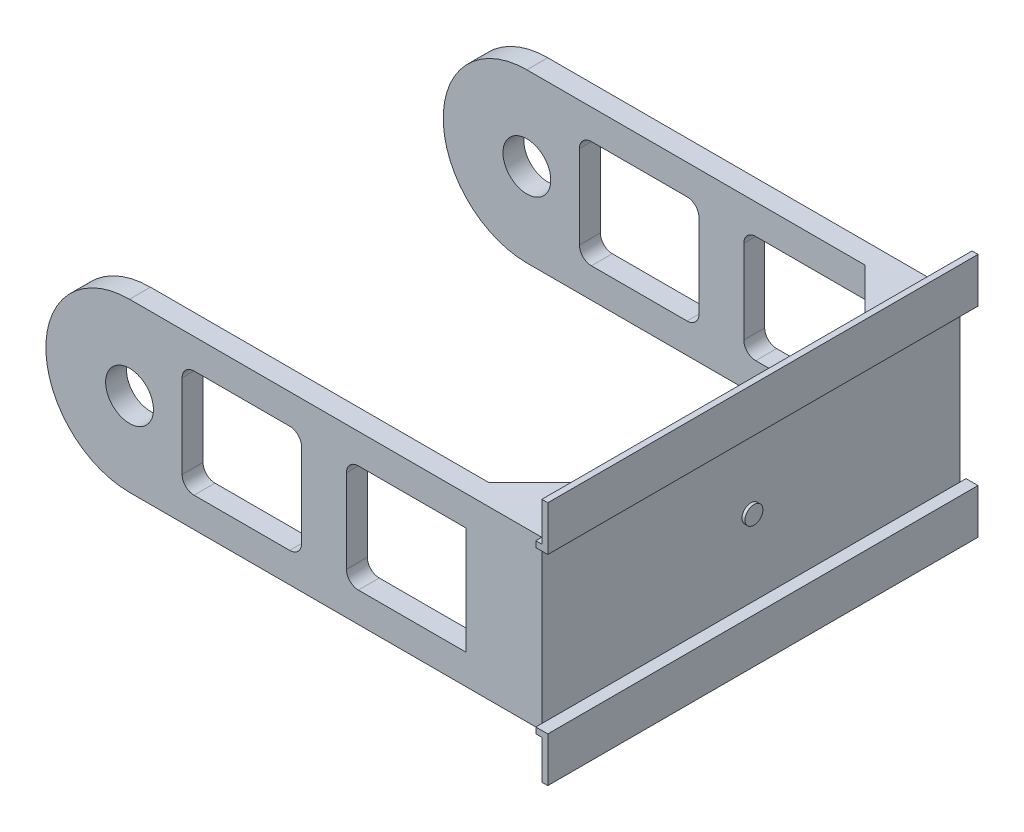
SolidWorks part; units mm, degrees
material "Plain Carbon Steel"
ref_plane "Front Plane" through (0, 0, 0) normal (0, 0, 1) x (1, 0, 0)
ref_plane "Top Plane" through (0, 0, 0) normal (0, 1, 0) x (1, 0, 0)
ref_plane "Right Plane" through (0, 0, 0) normal (1, 0, 0) x (0, 0, -1)
sketch "Sketch1" plane through (0, 0, 0) normal (0, 0, 1) x (1, 0, 0)
  line L0 (-36, 0) -> (33, 0) construction
  line L1 (-36, 14) -> (33, 14)
  line L2 (-36, -14) -> (33, -14)
  line L3 (33, 14) -> (33, -14)
  arc A0 (-36, 14) -> (-36, -14) centre (-36, 0) ccw
  circle A2 centre (-36, 0) radius 4
  point P2 (0, 0)
  dimension "D3" = 8
  dimension "D1" = 69
  dimension "D2" = 28
extrude "Boss-Extrude1" add sketch "Sketch1" along normal mid plane 70
sketch "Sketch3" plane through (0, 0, 0) normal (0, 0, 1) x (1, 0, 0)
  line L1 (-58.1267, 16.1907) -> (-13.8733, 16.1907)
  line L2 (-58.1267, 16.1907) -> (-58.1267, -16.1907)
  line L3 (-58.1267, -16.1907) -> (-13.8733, -16.1907)
  line L4 (-13.8733, 16.1907) -> (-13.8733, -16.1907)
  line L5 (-58.1267, 16.1907) -> (-13.8733, -16.1907) construction
  line L6 (-58.1267, -16.1907) -> (-13.8733, 16.1907) construction
  point P0 (-36, 0)
extrude "Cut-Extrude1" cut sketch "Sketch3" against normal mid plane 55
sketch "Sketch4" plane through (0, 14, 0) normal (0, 1, 0) x (1, 0, 0)
  line L0 (33, 35) -> (-36, 35) construction
  line L1 (-53.3457, 31.5) -> (30.5945, 31.5)
  line L2 (-53.3457, 31.5) -> (-53.3457, -31.5)
  line L3 (-53.3457, -31.5) -> (30.5945, -31.5)
  line L4 (30.5945, 31.5) -> (30.5945, -31.5)
  line L5 (33, -35) -> (-36, -35) construction
  dimension "D1" = 3.5
  dimension "D2" = 3.5
extrude "Cut-Extrude2" cut sketch "Sketch4" against normal through all
chamfer "Chamfer1" distance 10 angle 45 2 edges at (30.5945, 0, -31.5) (30.5945, 0, 31.5)
sketch "Sketch7" plane through (0, 0, 35) normal (0, 0, 1) x (1, 0, 0)
  line L0 (33, 14) -> (-36, 14) construction
  line L1 (-27.199, 9) -> (-7.199, 9)
  line L2 (-27.199, 9) -> (-27.199, -9)
  line L3 (-27.199, -9) -> (-7.199, -9)
  line L4 (-7.199, 9) -> (-7.199, -9)
  line L5 (-36, -14) -> (33, -14) construction
  line L7 (0.301, 9) -> (20.301, 9)
  line L8 (0.301, 9) -> (0.301, -9)
  line L9 (0.301, -9) -> (20.301, -9)
  line L10 (20.301, 9) -> (20.301, -9)
  dimension "D1" = 5
  dimension "D2" = 5
  dimension "D3" = 20
  dimension "D4" = 20
  dimension "D5" = 7.5
extrude "Cut-Extrude3" cut sketch "Sketch7" against normal through all
fillet "Fillet2" radius 2 14 edges at (-27.199, 9, 33.25) (-7.199, 9, 33.25) (-7.199, -9, 33.25) (-27.199, -9, 33.25) (0.301, 9, 33.25) (0.301, -9, 33.25) (20.301, 0, 31.5) (0.301, 9, -33.25) (0.301, -9, -33.25) (20.301, 0, -31.5) (-27.199, 9, -33.25) (-7.199, 9, -33.25) (-27.199, -9, -33.25) (-7.199, -9, -33.25)
sketch "Sketch10" plane through (0, 0, 35) normal (0, 0, 1) x (1, 0, 0)
  line L0 (33, 14) -> (34, 14)
  line L1 (34, 14) -> (34, 20.5)
  line L2 (33, 13) -> (35, 13)
  line L3 (35, 13) -> (35, 20.5)
  line L4 (33, 14) -> (33, 13)
  line L5 (38.5, 0) -> (-38.5, 0) construction
  line L6 (33, -14) -> (33, -13)
  line L7 (35, -13) -> (35, -20.5)
  line L8 (33, -13) -> (35, -13)
  line L9 (34, -14) -> (34, -20.5)
  line L10 (33, -14) -> (34, -14)
  line L11 (34, 20.5) -> (35, 20.5)
  line L12 (34, -20.5) -> (35, -20.5)
  dimension "D1" = 1
  dimension "D2" = 7.5
  dimension "D3" = 2
extrude "Boss-Extrude4" add sketch "Sketch10" against normal blind 72 from offset 1 contours L1 L11 L3 L2 L4 L0 | L8 L7 L12 L9 L10 L6
sketch "Sketch11" plane through (33, 0, 0) normal (1, 0, 0) x (0, 0, -1)
  circle A0 centre (0, 0) radius 1.5
  dimension "D1" = 3
extrude "Boss-Extrude5" add sketch "Sketch11" along normal blind 0.5
